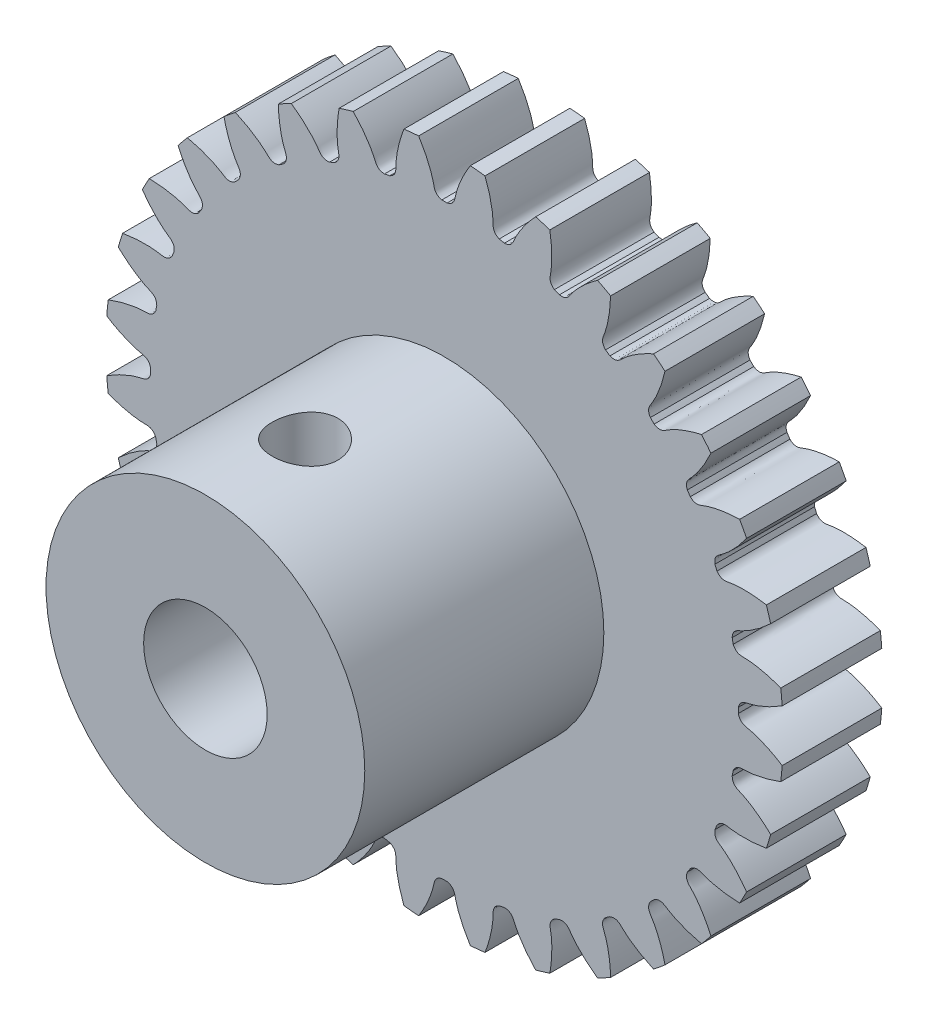
SolidWorks part; units mm, degrees
ref_plane "前视基准面" through (0, 0, 0) normal (0, 0, 1) x (1, 0, 0)
ref_plane "上视基准面" through (0, 0, 0) normal (0, 1, 0) x (1, 0, 0)
ref_plane "右视基准面" through (0, 0, 0) normal (1, 0, 0) x (0, 0, -1)
other "Configuration Table"
sketch "草图1" plane through (0, 0, 0) normal (0, 0, 1) x (1, 0, 0)
  circle A0 centre (0, 0) radius 8.5
extrude "凸台-拉伸1" add sketch "草图1" along normal blind 2.5
ref_axis "基准轴1" through (0, 0, 2.5) along (0, 0, -1)
sketch "草图2" plane through (0, 0, 0) normal (0, 0, 1) x (1, 0, 0)
  line L0 (0, 0) -> (0, 8.5) construction
  circle A0 centre (0, 0) radius 8.5 construction
  arc A1 (0.067, 7.3747) -> (-0.067, 7.3747) centre (0, 0) ccw
  arc A2 (1.6765, 9.6348) -> (-1.6765, 9.6348) centre (0, 0) ccw
  spline S0 degree 3 poles (0.067, 7.3747) (0.2444, 7.4176) (0.2542, 7.5462) (0.2867, 7.6804) (0.2952, 7.7127) (0.3051, 7.7477) (0.3166, 7.7854) (0.3299, 7.8257) (0.3449, 7.8686) (0.3618, 7.9139) (0.3807, 7.9618) (0.4017, 8.012) (0.4249, 8.0645) (0.4505, 8.1193) (0.4785, 8.1763) (0.509, 8.2353) (0.5421, 8.2964) (0.5779, 8.3594) (0.6164, 8.4243) (0.6579, 8.491) (0.7023, 8.5593) (0.7498, 8.6292) (0.8004, 8.7006) (0.8542, 8.7734) (0.9113, 8.8475) (0.9717, 8.9228) (1.0356, 8.9992) (1.1029, 9.0765) (1.1738, 9.1547) (1.2483, 9.2337) (1.3265, 9.3133) (1.4084, 9.3934) (1.5241, 9.5022) (1.6145, 9.5821) (1.6765, 9.6348) knots 0 0 0 0 0.124533 0.135329 0.147193 0.160126 0.174128 0.189198 0.205337 0.222544 0.24082 0.260164 0.280577 0.302059 0.324609 0.348227 0.372914 0.39867 0.425494 0.453386 0.482348 0.512377 0.543476 0.575642 0.608878 0.643181 0.678554 0.714995 0.752504 0.791082 0.830729 0.871444 0.913227 1 1 1 1
  spline S1 degree 3 poles (-0.067, 7.3747) (-0.2444, 7.4176) (-0.2542, 7.5462) (-0.2867, 7.6804) (-0.2952, 7.7127) (-0.3051, 7.7477) (-0.3166, 7.7854) (-0.3299, 7.8257) (-0.3449, 7.8686) (-0.3618, 7.9139) (-0.3807, 7.9618) (-0.4017, 8.012) (-0.4249, 8.0645) (-0.4505, 8.1193) (-0.4785, 8.1763) (-0.509, 8.2353) (-0.5421, 8.2964) (-0.5779, 8.3594) (-0.6164, 8.4243) (-0.6579, 8.491) (-0.7023, 8.5593) (-0.7498, 8.6292) (-0.8004, 8.7006) (-0.8542, 8.7734) (-0.9113, 8.8475) (-0.9717, 8.9228) (-1.0356, 8.9992) (-1.1029, 9.0765) (-1.1738, 9.1547) (-1.2483, 9.2337) (-1.3265, 9.3133) (-1.4084, 9.3934) (-1.5241, 9.5022) (-1.6145, 9.5821) (-1.6765, 9.6348) knots 0 0 0 0 0.124533 0.135329 0.147193 0.160126 0.174128 0.189198 0.205337 0.222544 0.24082 0.260164 0.280577 0.302059 0.324609 0.348227 0.372914 0.39867 0.425494 0.453386 0.482348 0.512377 0.543476 0.575642 0.608878 0.643181 0.678554 0.714995 0.752504 0.791082 0.830729 0.871444 0.913227 1 1 1 1
extrude "切除-拉伸1" cut sketch "草图2" along normal through all
pattern_circular "阵列(圆周)1" count 32 every 11.25 about axis through (0, 0, 2.5) along (0, 0, -1) of "切除-拉伸1"
sketch "草图3" plane through (0, 0, 0) normal (0, 0, 1) x (1, 0, 0)
  circle A0 centre (0, 0) radius 8 construction
  dimension "Dn" = 16
sketch "草图5" plane through (0, 0, 2.5) normal (0, 0, 1) x (1, 0, 0)
  circle A0 centre (0, 0) radius 4
  dimension "D1" = 8
extrude "凸台-拉伸2" add sketch "草图5" along normal blind 6
sketch "草图4" plane through (0, 0, 0) normal (0, 0, -1) x (-1, 0, 0)
  circle A0 centre (0, 0) radius 1.55
  dimension "D1" = 3.1
extrude "切除-拉伸2" cut sketch "草图4" against normal up to next
sketch "草图6" plane through (0, 0, 0) normal (0, 1, 0) x (1, 0, 0)
  line L0 (0, -8.5) -> (0, -2.5) construction
  line L1 (-4, -8.5) -> (4, -8.5) construction
  circle A0 centre (0, -6) radius 0.825
  dimension "D1" = 1.65
  dimension "D2" = 2.5
extrude "切除-拉伸3" cut sketch "草图6" along normal up to next
